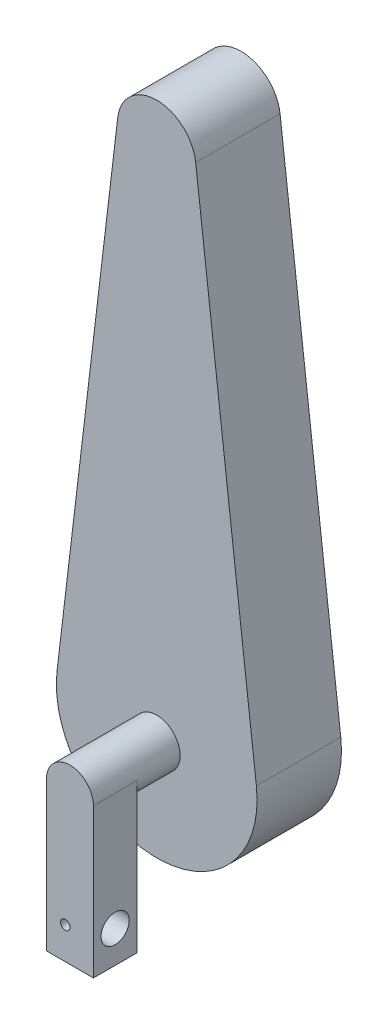
SolidWorks part; units mm, degrees
ref_plane "Front Plane" through (0, 0, 0) normal (1, 0, 0) x (0, 1, 0)
ref_plane "Top Plane" through (0, 0, 0) normal (0, 0, 1) x (0, 1, 0)
ref_plane "Right Plane" through (0, 0, 0) normal (0, 1, 0) x (-1, 0, 0)
sketch "Sketch1" plane through (0, 0, 0) normal (0, 0, 1) x (0, 1, 0)
  line L0 (-0.6386, 30.8368) -> (108.0393, 17.8929)
  line L1 (108.0393, 1.2654) -> (-0.6386, -11.6785)
  arc A2 (108.0393, 17.8929) -> (108.0393, 1.2654) centre (107.0491, 9.5791) cw
  arc A3 (-0.6386, -11.6785) -> (-0.6386, 30.8368) centre (-3.1705, 9.5791) cw
  dimension "D1" = 140
extrude "Boss-Extrude1" add sketch "Sketch1" along normal blind 18
sketch "Sketch2" plane through (0, 0, 18) normal (0, 0, 1) x (1, 0, 0)
  circle A0 centre (-9.5791, -3.1705) radius 5
  dimension "D1" = 10
extrude "Boss-Extrude2" add sketch "Sketch2" along normal blind 18.5
sketch "Sketch3" plane through (0, 0, 0) normal (0, 1, 0) x (-1, 0, 0)
  line L0 (4.5791, 36.5) -> (4.5791, 18) construction
  line L1 (14.5791, 36.5) -> (4.5791, 36.5)
  line L2 (14.5791, 36.5) -> (14.5791, 27.25)
  line L3 (14.5791, 27.25) -> (4.5791, 27.25)
  line L4 (4.5791, 36.5) -> (4.5791, 27.25)
extrude "Boss-Extrude3" add sketch "Sketch3" against normal blind 35
other "DeleteFace1" face at (-5.146, 0, 31.875) face at (-14.0123, 0, 31.875) and patch yes
sketch "Sketch4" plane through (-4.5791, 0, 0) normal (1, 0, 0) x (0, 1, 0)
  line L0 (-3.1705, 36.5) -> (-3.1705, 27.25) construction
  circle A0 centre (-28.1705, 31.875) radius 3
  point P4 (-3.1705, 31.875)
  dimension "D1" = 6
  dimension "D2" = 25
extrude "Cut-Extrude1" cut sketch "Sketch4" against normal through all
sketch "Sketch5" plane through (0, 0, 27.25) normal (0, 0, -1) x (1, 0, 0)
  line L0 (-4.5791, 35) -> (-4.5791, 3.1705) construction
  line L1 (-14.5791, 35) -> (-14.5791, 3.1705) construction
  line L2 (-4.5791, 35) -> (-14.5791, 35) construction
  line L3 (-4.5791, 35) -> (-4.5791, 3.1705) construction
  line L4 (-14.5791, 35) -> (-14.5791, 3.1705)
  line L5 (-4.5791, 35) -> (-14.5791, 35)
  line L8 (-4.5791, 25.1705) -> (-4.5791, 31.1705)
  line L9 (-4.5791, 25.1705) -> (-4.5791, 31.1705) construction
  circle A0 centre (-10.5791, 28.1705) radius 1
  point P4 (-10.5791, 28.1705)
  dimension "D2" = 2
  dimension "D1" = 10
  dimension "D3" = 6
  dimension "D4" = 0
extrude "Cut-Extrude4" cut sketch "Sketch5" against normal through all contours A0
